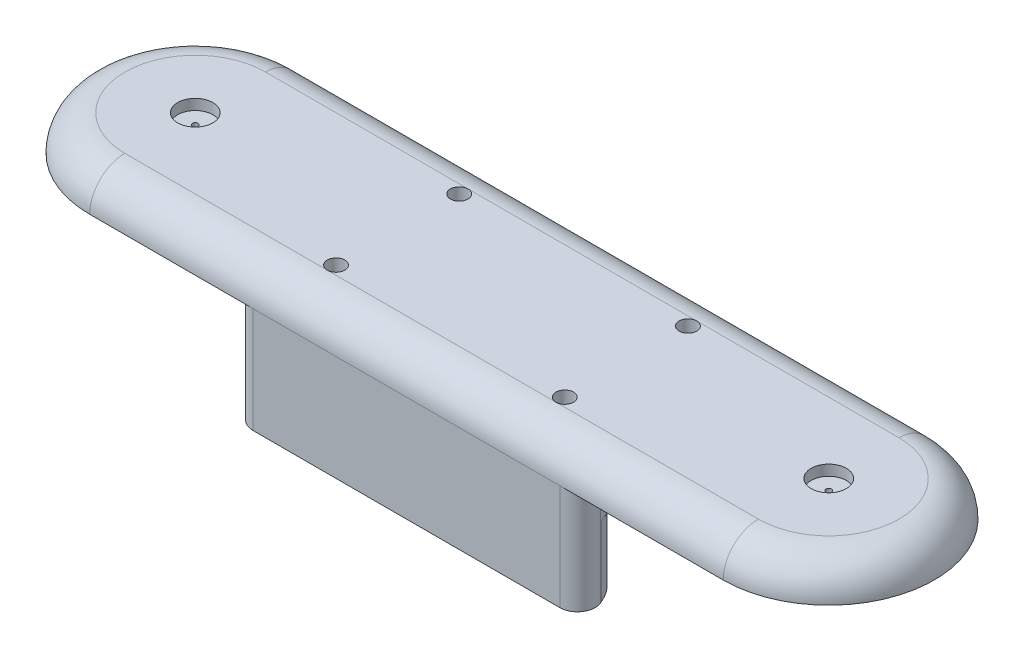
SolidWorks part; units mm, degrees
ref_plane "Front Plane" through (0, 0, 0) normal (0, 0, 1) x (1, 0, 0)
ref_plane "Top Plane" through (0, 0, 0) normal (0, 1, 0) x (1, 0, 0)
ref_plane "Right Plane" through (0, 0, 0) normal (1, 0, 0) x (0, 0, -1)
sketch "Sketch1" plane through (0, 0, 0) normal (0, 1, 0) x (1, 0, 0)
  line L0 (-67.6947, 31.5152) -> (112.3053, -28.4848) construction
  line L1 (-67.6947, 31.5152) -> (112.3053, 31.5152)
  line L3 (-67.6947, -28.4848) -> (112.3053, -28.4848)
  line L5 (112.3053, 31.5152) -> (-67.6947, -28.4848) construction
  line L6 (-67.6947, 31.5152) -> (-67.6947, -28.4848) construction
  arc A0 (-67.6947, 31.5152) -> (-67.6947, -28.4848) centre (-67.6947, 1.5152) ccw
  arc A1 (112.3053, 31.5152) -> (112.3053, -28.4848) centre (112.3053, 1.5152) cw
  point P6 (22.3053, 1.5152)
extrude "Boss-Extrude1" add sketch "Sketch1" along normal blind 40
fillet "Fillet1" radius 10 4 edges at (-97.6947, 40, -1.5152) (22.3053, 40, -31.5152) (142.3053, 40, -1.5152) (22.3053, 40, 28.4848)
sketch "Sketch3" plane through (0, 0, 0) normal (0, -1, 0) x (1, 0, 0)
  line L0 (112.3053, -31.5152) -> (-67.6947, -31.5152) construction
  line L5 (73.949, -31.5152) -> (148.949, -31.5152)
  line L6 (73.949, -31.5152) -> (73.949, 28.4848) construction
  line L7 (73.949, 28.4848) -> (148.949, 28.4848)
  line L8 (148.949, -31.5152) -> (148.949, 28.4848)
  line L9 (22.3053, 28.4848) -> (22.3053, -31.5152) construction
  line L10 (-67.6947, 28.4848) -> (112.3053, 28.4848) construction
  line L11 (-29.3384, -31.5152) -> (-29.3384, 28.4848) construction
  line L12 (-29.3384, 28.4848) -> (-104.3384, 28.4848)
  line L13 (-104.3384, -31.5152) -> (-104.3384, 28.4848)
  line L14 (-29.3384, -31.5152) -> (-104.3384, -31.5152)
  arc A2 (73.949, 28.4848) -> (73.949, -31.5152) centre (125.9106, -1.5152) ccw
  arc A3 (-29.3384, 28.4848) -> (-29.3384, -31.5152) centre (-81.3, -1.5152) cw
extrude "Cut-Extrude1" cut sketch "Sketch3" against normal blind 30
sketch "Sketch4" plane through (0, 30, 0) normal (0, -1, 0) x (-1, 0, 0)
  line L0 (67.6947, -28.4848) -> (67.6947, 31.5152) construction
  line L1 (-112.3053, -28.4848) -> (-112.3053, 31.5152) construction
  circle A0 centre (-112.3053, 1.5152) radius 10
  circle A1 centre (67.6947, 1.5152) radius 10
extrude "Boss-Extrude3" add sketch "Sketch4" along normal blind 10
ref_plane "Plane1" through (73.949, 0, 0) normal (1, 0, 0) x (0, 0, -1)
sketch "Sketch5" plane through (73.949, 0, 0) normal (1, 0, 0) x (0, 0, -1)
  line L0 (-28.4848, 0) -> (31.5152, 0) construction
  line L1 (11.5152, 20) -> (-8.4848, 20)
  line L2 (11.5152, 20) -> (11.5152, -20)
  line L3 (11.5152, -20) -> (-8.4848, -20)
  line L4 (-8.4848, 20) -> (-8.4848, -20)
  line L5 (11.5152, 20) -> (-8.4848, -20) construction
  line L6 (11.5152, -20) -> (-8.4848, 20) construction
  point P0 (1.5152, 0)
extrude "Cut-Extrude2" cut sketch "Sketch5" against normal up to next
fillet "Fillet2" radius 5 4 edges at (73.949, 15, 28.4848) (73.949, 15, -31.5152) (-29.3384, 15, -31.5152) (-29.3384, 15, 28.4848)
sketch "Sketch6" plane through (0, 0, 0) normal (0, -1, 0) x (-1, 0, 0)
  line L0 (-22.3053, -28.4848) -> (-22.3053, 31.5152) construction
  line L1 (21.3, -28.4848) -> (-65.9106, -28.4848) construction
  line L2 (-65.9106, 31.5152) -> (21.3, 31.5152) construction
  line L4 (10.1947, -15.9848) -> (-54.8053, -15.9848) construction
  line L5 (10.1947, -15.9848) -> (10.1947, 19.0152) construction
  line L6 (10.1947, 19.0152) -> (-54.8053, 19.0152) construction
  line L7 (-54.8053, -15.9848) -> (-54.8053, 19.0152) construction
  line L8 (10.1947, -15.9848) -> (-54.8053, 19.0152) construction
  line L9 (10.1947, 19.0152) -> (-54.8053, -15.9848) construction
  circle A0 centre (10.1947, -15.9848) radius 1
  circle A1 centre (-54.8053, -15.9848) radius 1
  circle A2 centre (-54.8053, 19.0152) radius 1
  circle A3 centre (10.1947, 19.0152) radius 1
  point P6 (-22.3053, 1.5152)
extrude "Cut-Extrude3" cut sketch "Sketch6" against normal up to next
sketch "Sketch7" plane through (0, 40, 0) normal (0, 1, 0) x (1, 0, 0)
  circle A0 centre (-10.1947, 19.0152) radius 2.5
  circle A1 centre (-10.1947, -15.9848) radius 2.5
  circle A2 centre (54.8053, -15.9848) radius 2.5
  circle A3 centre (54.8053, 19.0152) radius 2.5
extrude "Cut-Extrude4" cut sketch "Sketch7" against normal blind 5
sketch "Sketch8" plane through (0, 20, 0) normal (0, -1, 0) x (-1, 0, 0)
  circle A0 centre (67.6947, 1.5152) radius 0.8
  circle A1 centre (-112.3053, 1.5152) radius 0.8
extrude "Cut-Extrude5" cut sketch "Sketch8" against normal up to next
sketch "Sketch9" plane through (0, 20, 0) normal (0, -1, 0) x (-1, 0, 0)
  circle A0 centre (67.6947, 1.5152) radius 3
  circle A1 centre (-112.3053, 1.5152) radius 3
extrude "Cut-Extrude6" cut sketch "Sketch9" against normal blind 10
sketch "Sketch11" plane through (0, 40, 0) normal (0, 1, 0) x (1, 0, 0)
  circle A0 centre (-67.6947, 1.5152) radius 5
  circle A1 centre (112.3053, 1.5152) radius 5
extrude "Cut-Extrude7" cut sketch "Sketch11" against normal blind 3
sketch "Sketch12" plane through (0, 0, 0) normal (0, -1, 0) x (-1, 0, 0)
  circle A0 centre (22.1392, -8.4848) radius 6
  circle A1 centre (22.1392, 11.5152) radius 6
  circle A2 centre (-66.7498, 11.5152) radius 6
  circle A3 centre (-66.7498, -8.4848) radius 6
extrude "Cut-Extrude8" cut sketch "Sketch12" against normal blind 20
fillet "Fillet3" radius 15 8 edges at (-23.4337, 10, -17.3738) (-16.1392, 10, -11.5152) (60.7498, 10, -11.5152) (68.0443, 10, -17.3738) (68.0443, 10, 14.3435) (60.7498, 10, 8.4848) (-16.1392, 10, 8.4848) (-23.4337, 10, 14.3435)
